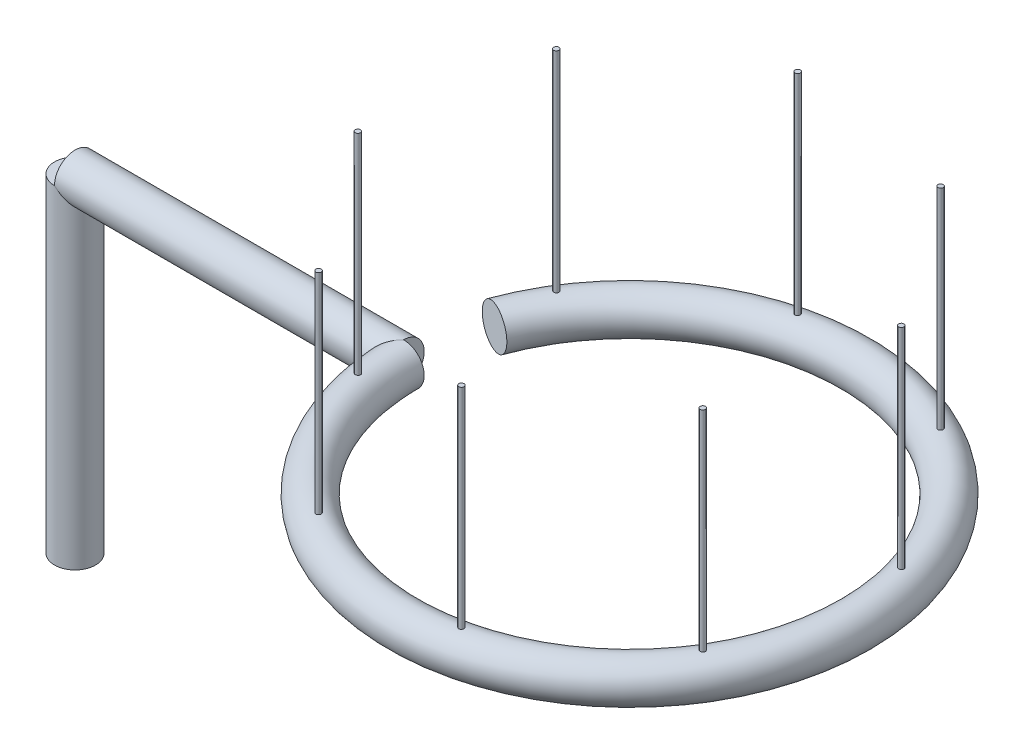
SolidWorks part; units mm, degrees
ref_plane "Front Plane" through (0, 0, 0) normal (0, 0, 1) x (1, 0, 0)
ref_plane "Top Plane" through (0, 0, 0) normal (0, 1, 0) x (1, 0, 0)
ref_plane "Right Plane" through (0, 0, 0) normal (1, 0, 0) x (0, 0, -1)
sketch "Sketch1" plane through (0, 0, 0) normal (0, 0, 1) x (1, 0, 0)
  line L0 (0, 0) -> (0, 18.499) construction
  circle A0 centre (-34.925, 0) radius 3.175
  dimension "D1" = 6.35
  dimension "D2" = 34.925
revolve "Revolve1" add sketch "Sketch1" angle 340 about L0
sketch "Sketch3" plane through (0, 0, 0) normal (0, 0, 1) x (1, 0, 0)
  line L0 (0, 0) -> (0, 35.0105) construction
sketch "Sketch2" plane through (0, 0, 0) normal (0, 1, 0) x (1, 0, 0)
  circle A0 centre (-29.6974, 18.3799) radius 0.4096
  dimension "D2" = 0.8192
  dimension "D1" = 34.925
extrude "Boss-Extrude1" add sketch "Sketch2" along normal blind 35.56
pattern_circular "CirPattern1" count 8 over 360 about axis through (0, 0, 0) along (0, 1, 0) of "Boss-Extrude1" reverse direction yes
sketch "Sketch6" plane through (0, 0, 0) normal (0, 0, -1) x (-1, 0, 0)
  line L0 (34.925, 0) -> (42.9594, 0) construction
  line L1 (34.925, 0) -> (34.925, 7.5759) construction
ref_plane "Plane1" through (-34.925, 0, 0) normal (-1, 0, 0) x (0, 1, 0)
sketch "Sketch7" plane through (-34.925, 0, 0) normal (-1, 0, 0) x (0, 1, 0)
  circle A0 centre (0, 0) radius 3.175
extrude "Boss-Extrude2" add sketch "Sketch7" along normal blind 50.8
sketch "Sketch8" plane through (0, 0, 0) normal (0, 0, -1) x (-1, 0, 0)
  line L0 (34.925, 0) -> (34.925, 7.5759) construction
  line L1 (34.925, 3.175) -> (34.925, -3.175)
  arc A0 (34.925, 3.175) -> (34.925, -3.175) centre (34.925, 0) ccw
  arc A1 (34.925, 3.175) -> (34.925, -3.175) centre (34.925, 0) ccw construction
sketch "Sketch9" plane through (-85.725, 0, 0) normal (-1, 0, 0) x (0, 0, 1)
  line L0 (0, 0) -> (-13.2854, 0) construction
  line L2 (0, 3.175) -> (0, -3.175) construction
ref_plane "Plane2" through (0, 0, 0) normal (0, 1, 0) x (0, 0, -1)
sketch "Sketch10" plane through (0, 0, 0) normal (0, 1, 0) x (0, 0, -1)
  line L0 (3.175, 85.725) -> (-3.175, 85.725) construction
  circle A0 centre (0, 85.725) radius 3.175
extrude "Boss-Extrude3" add sketch "Sketch10" against normal blind 50.8
sketch "Sketch12" plane through (0, 0, 0) normal (0, 1, 0) x (1, 0, 0)
  circle A0 centre (0, 0) radius 17.8974 construction
